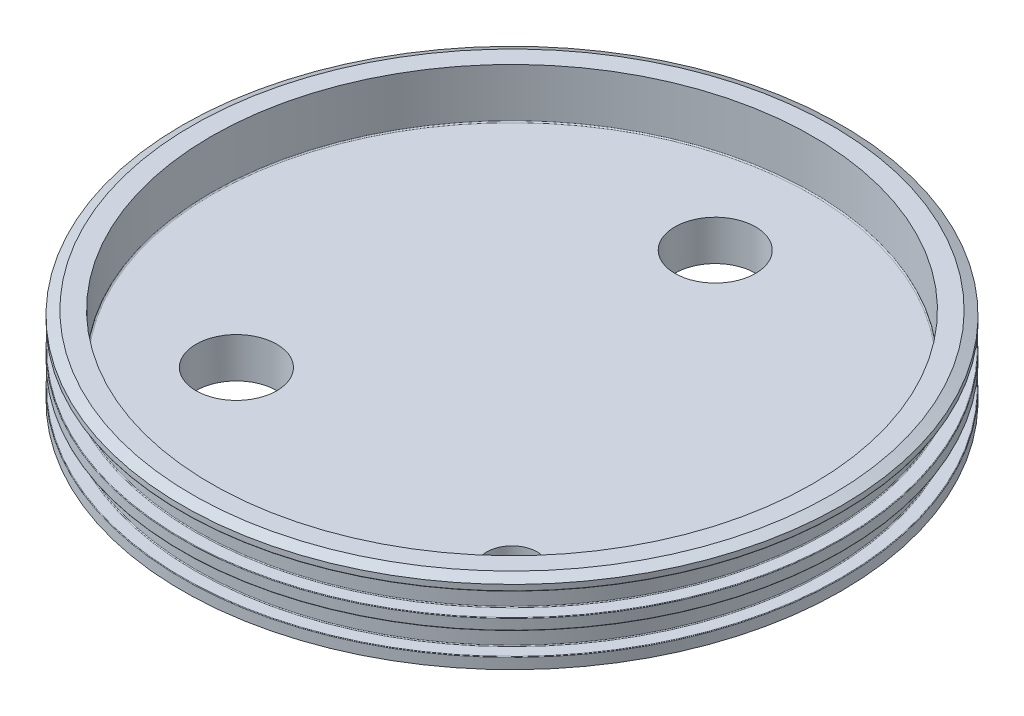
SolidWorks part; units mm, degrees
material "6061-T6 (SS)"
ref_plane "Front Plane" through (0, 0, 0) normal (0, 0, 1) x (1, 0, 0)
ref_plane "Top Plane" through (0, 0, 0) normal (0, 1, 0) x (1, 0, 0)
ref_plane "Right Plane" through (0, 0, 0) normal (1, 0, 0) x (0, 0, -1)
sketch "Sketch1" plane through (0, 0, 0) normal (0, 0, 1) x (1, 0, 0)
  line L0 (0, 48.1922) -> (0, -25.6743) construction
  line L1 (0, 0) -> (72.898, 0)
  line L2 (72.898, 0) -> (72.898, 2.4638)
  line L3 (72.898, 2.4638) -> (69.977, 2.4638)
  line L4 (69.977, 2.4638) -> (69.977, 7.4422)
  line L5 (69.977, 7.4422) -> (72.898, 7.4422)
  line L6 (72.898, 7.4422) -> (72.898, 9.906)
  line L7 (72.898, 9.906) -> (69.977, 9.906)
  line L8 (66.548, 17.3482) -> (66.548, 6.35)
  line L9 (66.548, 6.35) -> (0, 6.35)
  line L10 (0, 6.35) -> (0, 0)
  line L11 (69.977, 9.906) -> (69.977, 14.986)
  line L12 (69.977, 14.986) -> (72.898, 14.986)
  line L13 (72.898, 14.986) -> (72.898, 17.3482)
  line L14 (72.898, 17.3482) -> (66.548, 17.3482)
  dimension "D1" = 145.796
  dimension "D2" = 4.9784
  dimension "D3" = 2.921
  dimension "D4" = 9.906
  dimension "D5" = 6.35
  dimension "D6" = 6.35
  dimension "D7" = 5.08
  dimension "D8" = 9.906
revolve "Revolve1" add sketch "Sketch1" angle 360 about L0
sketch "Sketch6" plane through (0, 0, 0) normal (0, -1, 0) x (1, 0, 0)
  circle A0 centre (0, 0) radius 66.04
  dimension "D1" = 132.08
extrude "Boss-Extrude1" add sketch "Sketch6" along normal blind 2.54
fillet "CNC ID Fillet" radius 0.1778 5 edges at (-69.977, 7.4422, 0) (-69.977, 2.4638, 0) (66.04, 0, 0) (-69.977, 14.986, 0) (-69.977, 9.906, 0)
fillet "CNC OD Fillet" radius 0.127 5 edges at (-72.898, 7.4422, 0) (-72.898, 2.4638, 0) (-72.898, 9.906, 0) (-72.898, 14.986, 0) (66.04, -2.54, 0)
chamfer "CNC Chamfers" distance 1.016 angle 65 1 edges at (-72.898, 17.3482, 0) first distance on face at (-72.898, 15.113, 0)
fillet "CNC Bore Fillet" radius 0.254 1 edges at (-66.548, 6.35, 0)
hole_wizard "Pipe Tap Drill for 1/2 Tap - Fill Valve" positions "Sketch13" profile "Sketch14" hole size "1/2" standard "ANSI Inch" end condition through all
sketch "Sketch13" plane through (0, -2.54, 0) normal (0, -1, 0) x (-1, 0, 0)
  point P4 (0, 44.958)
  dimension "D1" = 44.958
sketch "Sketch14" plane through (0, -2.54, -44.958) normal (1, 0, 0) x (0, 0, -1)
  line L0 (0, 0) -> (0, 19.8882)
  line L1 (0, 19.8882) -> (8.9281, 19.8882)
  line L2 (8.9281, 19.8882) -> (8.9281, 0)
  line L5 (8.9281, 0) -> (0, 0)
  line L11 (0, -6.35) -> (0, 107.95) construction
  dimension "Thru Hole Dia." = 17.8562
  dimension "Thru Hole Depth" = 19.8882
hole_wizard "Pipe Tap Drill for 1/4 Tap - Solenoid Valve" positions "Sketch15" profile "Sketch16" hole size "1/4" standard "ANSI Inch" end condition through all
sketch "Sketch15" plane through (0, -2.54, 0) normal (0, -1, 0) x (-1, 0, 0)
  point P4 (-38.1, -38.1)
  dimension "D1" = 38.1
  dimension "D2" = 38.1
sketch "Sketch16" plane through (38.1, -2.54, 38.1) normal (1, 0, 0) x (0, 0, -1)
  line L0 (0, 0) -> (0, 19.8882)
  line L1 (0, 19.8882) -> (5.5626, 19.8882)
  line L2 (5.5626, 19.8882) -> (5.5626, 0)
  line L5 (5.5626, 0) -> (0, 0)
  line L11 (0, -6.35) -> (0, 107.95) construction
  dimension "Thru Hole Dia." = 11.1252
  dimension "Thru Hole Depth" = 19.8882
hole_wizard "Pipe Tap Drill for 1/2 Tap - Cryo Valve" positions "Sketch17" profile "Sketch18" hole size "1/2" standard "ANSI Inch" end condition through all
sketch "Sketch17" plane through (0, -2.54, 0) normal (0, -1, 0) x (-1, 0, 0)
  point P4 (30.48, -30.48)
  dimension "D1" = 30.48
  dimension "D2" = 30.48
sketch "Sketch18" plane through (-30.48, -2.54, 30.48) normal (1, 0, 0) x (0, 0, -1)
  line L0 (0, 0) -> (0, 19.8882)
  line L1 (0, 19.8882) -> (8.9281, 19.8882)
  line L2 (8.9281, 19.8882) -> (8.9281, 0)
  line L5 (8.9281, 0) -> (0, 0)
  line L11 (0, -6.35) -> (0, 107.95) construction
  dimension "Thru Hole Dia." = 17.8562
  dimension "Thru Hole Depth" = 19.8882
